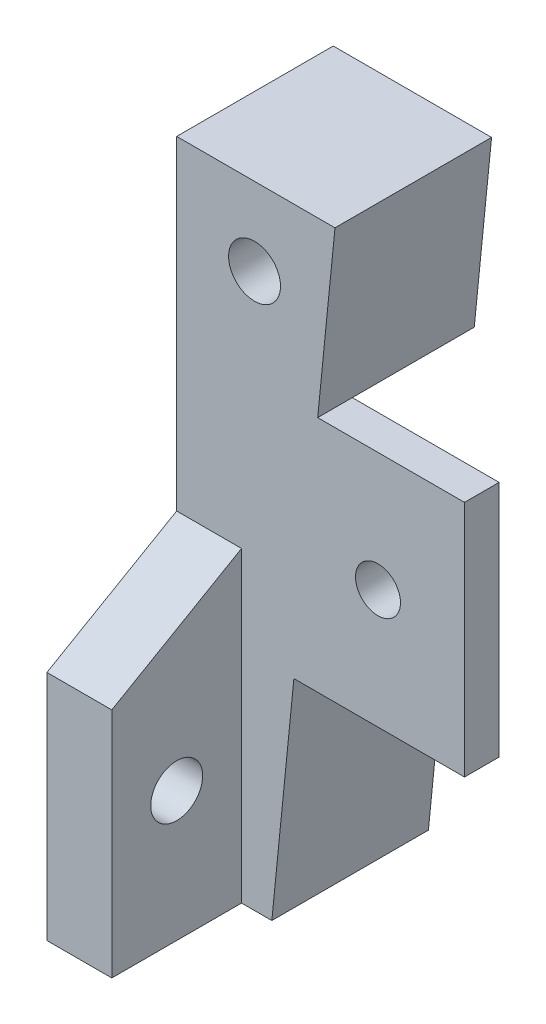
SolidWorks part; units mm, degrees
ref_plane "Front Plane" through (0, 0, 0) normal (0, 0, 1) x (1, 0, 0)
ref_plane "Top Plane" through (0, 0, 0) normal (0, 1, 0) x (1, 0, 0)
ref_plane "Right Plane" through (0, 0, 0) normal (1, 0, 0) x (0, 0, -1)
sketch "Sketch1" plane through (0, 0, 0) normal (0, 0, 1) x (1, 0, 0)
  line L0 (125, -375) -> (127.55, -349.5)
  line L1 (100, -349.5) -> (240, -349.5) construction
  line L2 (125, -375) -> (150, -125) construction
  line L3 (127.55, -349.5) -> (114, -349.5)
  line L4 (114, -300) -> (114, -375) construction
  line L5 (114, -349.5) -> (114, -375)
  line L6 (114, -375) -> (125, -375)
  line L7 (132.3, -302) -> (130.3, -322)
  line L8 (196.9515, -322) -> (114, -322) construction
  line L9 (130.3, -322) -> (114, -322)
  line L10 (114, -322) -> (114, -302)
  line L11 (114, -302) -> (132.3, -302)
  dimension "D1" = 20
extrude "Boss-Extrude1" add sketch "Sketch1" along normal up to surface (14.1 mm away)
sketch "Sketch2" plane through (0, 0, 14.1) normal (0, 0, 1) x (1, 0, 0)
  line L0 (114, -302) -> (132.3, -302)
  line L1 (132.3, -302) -> (125, -375)
  line L2 (125, -375) -> (114, -375)
  line L3 (114, -375) -> (114, -302)
  line L4 (130.3, -322) -> (142.27, -322)
  line L5 (196.9515, -322) -> (114, -322) construction
  line L6 (142.27, -323) -> (142.27, -348)
  line L7 (114.0043, -348) -> (142.27, -348) construction
  line L8 (142.27, -348) -> (142.27, -323) construction
  line L9 (142.27, -348) -> (142.27, -349.5)
  line L10 (100, -349.5) -> (240, -349.5) construction
  line L11 (142.27, -349.5) -> (127.55, -349.5)
  line L12 (142.27, -323) -> (142.27, -322)
  line M5 (114, -349.5) -> (114, -375)
  line M6 (114, -375) -> (125, -375)
  line M7 (125, -375) -> (127.55, -349.5)
  line M8 (127.55, -349.5) -> (114, -349.5)
extrude "Boss-Extrude2" add sketch "Sketch2" along normal blind 4 contours L6 L12 L4 L1 L11 L9 | M8 M5 M6 M7 | L3 L1 L0 M8 region at (122.0215, -324.5693, 14.1) region at (120.1596, -361.8086, 14.1) region at (135.5739, -336.2222, 14.1)
sketch "Sketch3" plane through (142.27, 0, 0) normal (1, 0, 0) x (0, 0, -1)
  line L0 (-18.1, -349.5) -> (-14.1, -349.5) construction
  line L1 (-18.1, -322) -> (-14.1, -322)
  line L2 (-18.1, -322) -> (-18.1, -349.5)
  line L3 (-18.1, -349.5) -> (-14.1, -349.5)
  line L4 (-14.1, -322) -> (-14.1, -349.5)
  line L5 (-14.1, -322) -> (-14.1, -349.5) construction
extrude "Boss-Extrude3" add sketch "Sketch3" along normal blind 5
sketch "Sketch4" plane through (0, 0, 18.1) normal (0, 0, 1) x (1, 0, 0)
  line L0 (114, -375) -> (114, -302) construction
  line L1 (130.3, -322) -> (147.27, -322) construction
  line L4 (114, -302) -> (132.3, -302) construction
  circle A0 centre (137.27, -335.75) radius 2.6
  circle A1 centre (123, -311) radius 3
  dimension "D1" = 5.2
  dimension "D4" = 6
  dimension "D2" = 23.27
  dimension "D3" = 13.75
  dimension "D5" = 9
  dimension "D6" = 9
extrude "Cut-Extrude1" cut sketch "Sketch4" against normal blind 35
sketch "Sketch5" plane through (0, 0, 18.1) normal (0, 0, 1) x (1, 0, 0)
  line L1 (114, -375) -> (121.5, -375)
  line L2 (114, -375) -> (114, -349.5)
  line L3 (114, -349.5) -> (121.5, -349.5)
  line L4 (121.5, -375) -> (121.5, -349.5)
  point P5 (0, 0)
  point P7 (0, 0)
  point P8 (0, 0)
  point P9 (0, 0)
  dimension "D1" = 7.5
extrude "Boss-Extrude4" add sketch "Sketch5" along normal blind 15
chamfer "Chamfer1" distance 10 angle 60 1 edges at (117.75, -349.5, 18.1) first distance on face at (128.069, -339.6, 18.1)
hole_wizard "Ø6.0 (6) Diameter Hole1" positions "Sketch6" profile "Sketch7" hole size "Ø6.0" standard "ANSI Metric" end condition through all
sketch "Sketch6" plane through (121.5, 0, 0) normal (1, 0, 0) x (0, 0, -1)
  line L0 (-33.1, -375) -> (-33.1, -348.1603) construction
  line L1 (-33.1, -375) -> (-18.1, -375) construction
  point P0 (-25.6, -360)
  dimension "D1" = 7.5
  dimension "D2" = 15
sketch "Sketch7" plane through (121.5, -360, 25.6) normal (0, 1, 0) x (0, 0, -1)
  line L0 (0, 0) -> (0, 7.5)
  line L1 (0, 7.5) -> (3, 7.5)
  line L2 (3, 7.5) -> (3, 0)
  line L5 (3, 0) -> (0, 0)
  line L11 (0, -6.35) -> (0, 107.95) construction
  dimension "Thru Hole Dia." = 6
  dimension "Thru Hole Depth" = 7.5
